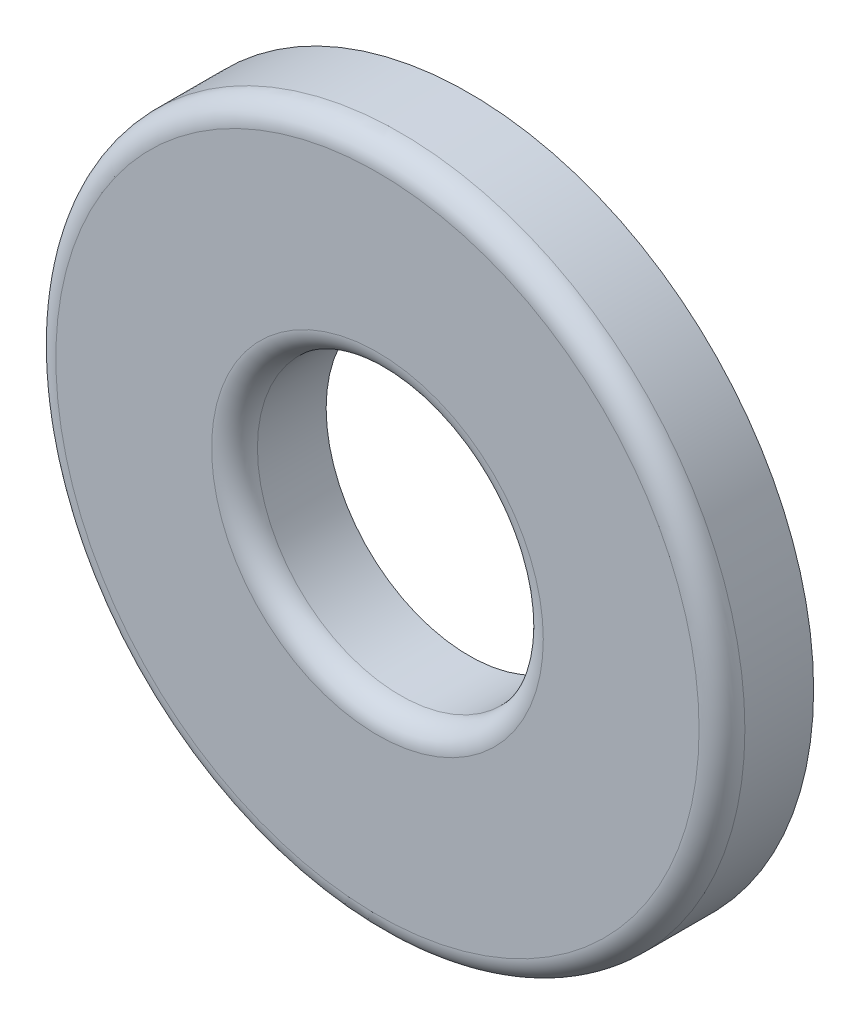
SolidWorks part; units mm, degrees
note: '?' marks a value the reader was unsure of.
other "Imported1" parameters "D1"=0.1588, "TH"=1.0287, "Thickness"=0.635
ref_plane "Front Plane" through (0, 0, 0) normal (0, 0, 1) x (1, 0, 0)
ref_plane "Top Plane" through (0, 0, 0) normal (0, 1, 0) x (1, 0, 0)
ref_plane "Right Plane" through (0, 0, 0) normal (1, 0, 0) x (0, 0, -1)
sketch "Sketch1" plane through (0, 0, 0) normal (0, 0, 1) x (1, 0, 0)
  line L0 (-2.3876, 0) -> (2.3876, 0) construction
  line L1 (-0.9906, 0) -> (0.9906, 0) construction
  circle A0 centre (0, 0) radius 0.9906 construction
  circle A1 centre (0, 0) radius 2.3876 construction
  point P8 (0, 0)
  point P9 (0, 2.3876)
  point P11 (0.9906, 0)
  dimension "ID" = 1.9812
  dimension "OD" = 4.7752
sketch "Sketch2" plane through (0, 0, 0) normal (1, 0, 0) x (0, 0, -1)
  line L0 (-0.3175, 2.3876) -> (0.3175, 2.3876) construction
  point P2 (0, 2.3876)
sketch "Sketch3" plane through (0, 0, 0) normal (0, 0, 1) x (1, 0, 0)
  circle A0 centre (0, 0) radius 0.9906
  circle A1 centre (0, 0) radius 2.3876
extrude "Boss-Extrude1" add sketch "Sketch3" along normal up to vertex (0.3175 mm away) and the other way up to vertex (0.3175 mm away) up to point (0, 2.3876, 0.3175) other way up to point (0, 2.3876, -0.3175)
fillet "Fillet1" radius 0.1588 2 edges at (2.3876, 0, 0.3175) (0.9906, 0, 0.3175)
ref_axis "Center Axis 1" through (0, 0, 0.1587) along (0, 0, -1)?
equation "\"D1@Fillet1\"=\"Thickness@Sketch2\"/4"
